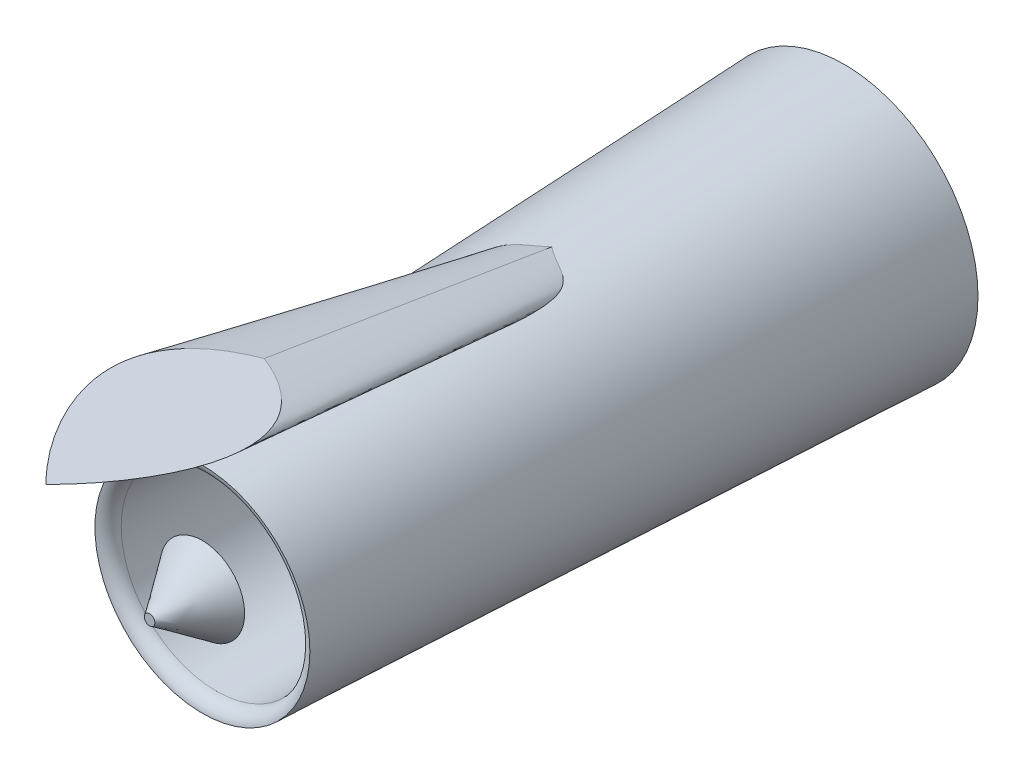
SolidWorks part; units mm, degrees
ref_plane "Front Plane" through (0, 0, 0) normal (0, 0, 1) x (1, 0, 0)
ref_plane "Top Plane" through (0, 0, 0) normal (0, 1, 0) x (1, 0, 0)
ref_plane "Right Plane" through (0, 0, 0) normal (1, 0, 0) x (0, 0, -1)
sketch "Sketch2" plane through (0, 0, 0) normal (0, 1, 0) x (1, 0, 0)
  line L0 (0, -5194.446) -> (0, 1731.482)
  line L1 (0, 0) -> (-18096.1342, 0) construction
  line L2 (0, 0) -> (-22098, -13277.818) construction
  line L3 (-22098, -15095.8741) -> (-22098, -12671.7993)
  line L4 (-22098, -12671.7993) -> (0, 1731.482)
  line L5 (-22098, -15095.8741) -> (0, -5194.446)
  line L6 (-9275.7037, -4314.3398) -> (-9275.7037, -5573.4051) construction
  line L7 (-9275.7037, -5573.4051) -> (-9275.7037, -9350.601) construction
  line L8 (-9275.7037, -5573.4051) -> (0, -5573.4051) construction
  line L9 (0, 346.2964) -> (-6827.52, -3825.6374)
  line L10 (0, -29565.6) -> (-7316.724, -34881.5112) construction
  line L11 (0, -29565.6) -> (-8167.6786, -29565.6) construction
  line L12 (0, -28507.0982) -> (0, -32741.1055)
  line L13 (-7316.724, -35992.9378) -> (-7316.724, -34511.0356)
  line L14 (-7316.724, -34511.0356) -> (0, -28507.0982)
  line L15 (0, -32741.1055) -> (-7316.724, -35992.9378)
  line L16 (-2399.2704, -30475.8849) -> (-2399.2704, -31308.772) construction
  line L17 (-2399.2704, -31308.772) -> (-2399.2704, -33807.4331) construction
  line L18 (-2399.2704, -31308.772) -> (0, -31308.772) construction
  line L19 (-6827.52, -3825.6374) -> (-6827.52, -6593.1427)
  line L20 (-6827.52, -6593.1427) -> (0, -3116.6676)
  line L21 (0, 346.2964) -> (0, -3116.6676) construction
  line L22 (0, -3116.6676) -> (0, 346.2964) construction
  line L23 (0, 346.2964) -> (0, -1385.1856) construction
  line L24 (0, 346.2964) -> (0, -3116.6676) construction
  line L25 (0, -1385.1856) -> (-6827.52, -5209.39) construction
  line L26 (0, 346.2964) -> (-22098, -13156.6142) construction
  line L27 (-3160.776, -1585.0854) -> (-3160.776, -3155.5874) construction
  line L28 (-3160.776, -3155.5874) -> (-3160.776, -4726.0893) construction
  line L29 (-3160.776, -3155.5874) -> (0, -3155.5874) construction
  dimension "Wing Sweep" = 31
  dimension "Half Span" = 22098
  dimension "Wing Root" = 6925.928
  dimension "D4" = 1731.482
  dimension "Wing Tip" = 2424.0748
  dimension "D6" = 606.0187
  dimension "Wing YBar" = 9275.7037
  dimension "Tail Sweep" = 36
  dimension "Tail Root" = 4234.0073
  dimension "D10" = 1058.5018
  dimension "Tail Tip" = 1481.9022
  dimension "D12" = 370.4756
  dimension "D13" = 7316.724
  dimension "Tail Ybar" = 2399.2704
  dimension "First Spar" = 1385.1856
  dimension "Second Spar" = 4848.1496
  dimension "Fuel Tip" = 2767.5053
  dimension "Tip Spar" = 484.815
  dimension "Fuel Ybar" = 3160.776
  dimension "Fuel Tank Length" = 6827.52
  dimension "Tail Arm" = 29565.6
sketch "Sketch4" plane through (0, 0, 0) normal (0, 1, 0) x (1, 0, 0)
  line L0 (0, 18200.9949) -> (0, -34834.2051) construction
  line L1 (-2240.28, 18200.9949) -> (2240.28, 18200.9949) construction
  line L2 (-2240.28, 11480.1549) -> (-2240.28, -25873.0851)
  line L3 (-2240.28, -34834.2051) -> (2240.28, -34834.2051) construction
  line L4 (2240.28, 11480.1549) -> (2240.28, -25873.0851)
  line L5 (0, -5194.446) -> (0, 1731.482) construction
  line L6 (-9275.7037, -5573.4051) -> (0, -5573.4051) construction
  line L7 (-2399.2704, -31308.772) -> (0, -31308.772) construction
  line L8 (0, 0) -> (-22098, -13277.818) construction
  line L9 (-22098, -12671.7993) -> (0, 1731.482) construction
  line L10 (-8451.85, 1616.4392) -> (-6132.83, 1616.4392)
  line L11 (-8451.85, 1616.4392) -> (-8451.85, -3941.0808)
  line L12 (-8451.85, -3941.0808) -> (-6132.83, -3941.0808)
  line L13 (-6132.83, 1616.4392) -> (-6132.83, -3941.0808)
  line L14 (2240.28, 11480.1549) -> (-2240.28, 11480.1549)
  arc A0 (-2240.28, -25873.0851) -> (2240.28, -25873.0851) centre (0, -25873.0851) ccw construction
  spline S0 degree 2 poles (-2240.28, 11480.1549) (-2010.8321, 15064.3252) (0, 18200.9949) knots 0 0 0 1 1 1 construction
  spline S1 degree 2 poles (2240.28, 11480.1549) (2010.8321, 15064.3252) (0, 18200.9949) knots 0 0 0 1 1 1 construction
  spline S2 degree 3 poles (-2240.28, -25873.0851) (-2042.135, -27711.7659) (-2075.1921, -30173.7144) (-919.8513, -32825.3563) (0, -32741.1055) knots 0 0 0 0 0.711043 1 1 1 1 construction
  spline S3 degree 3 poles (2240.28, -25873.0851) (2042.135, -27711.7659) (2075.1921, -30173.7144) (919.8513, -32825.3563) (0, -32741.1055) knots 0 0 0 0 0.711043 1 1 1 1 construction
  spline S4 degree 2 poles (-2240.28, -25873.0851) (-2027.1744, -27637.7456) (0, -27753.3552) knots 0 0 0 1 1 1
  spline S5 degree 2 poles (2240.28, -25873.0851) (2027.1744, -27637.7456) (0, -27753.3552) knots 0 0 0 1 1 1
  point P6 (0, 11480.1549)
  point P7 (0, -25873.0851)
  point P8 (0, -5573.4051)
  point P15 (0, -28113.3651)
  point P28 (-7292.34, 1616.4392)
  point P29 (-7292.34, -3021.6008)
  point P35 (-7292.34, -4381.6799)
  point P44 (-7292.34, -606.5688)
  dimension "Fuse Length" = 53035.2
  dimension "Fuse Dia" = 4480.56
  dimension "D3" = 6720.84
  dimension "D4" = 8961.12
  dimension "D6" = 7292.34
  dimension "Engine Dia" = 2319.02
  dimension "Engine Length" = 5557.52
  dimension "D9" = 4638.04
  dimension "D10" = 2223.008
  dimension "D11" = 4966.8362
  dimension "D2" = 23774.4
ref_plane "Plane1" through (0, 609.6, 0) normal (0, 1, 0) x (1, 0, 0)
sketch "Sketch10" plane through (0, 0, 0) normal (0, 1, 0) x (1, 0, 0)
  line L0 (-22098, -12671.7993) -> (-2240.28, 271.2873)
  line L1 (-2240.28, 11480.1549) -> (-2240.28, -25873.0851) construction
  line L2 (-22098, -12671.7993) -> (-22098, -15095.8741)
  line L3 (-22098, -15095.8741) -> (-7292.34, -8461.9172)
  line L4 (-7292.34, -8461.9172) -> (-2240.28, -8461.9172)
  line L5 (-22098, -15095.8741) -> (0, -5194.446) construction
  line L6 (-22098, -12671.7993) -> (0, 1731.482) construction
  line L7 (-2240.28, -8461.9172) -> (-2240.28, 271.2873) construction
  line L9 (0, 271.2873) -> (0, -8461.9172)
  line L10 (0, -8461.9172) -> (-2240.28, -8461.9172)
  line L11 (0, -5194.446) -> (0, 1731.482) construction
  line L12 (-2240.28, 271.2873) -> (0, 1731.482)
  line L13 (0, 1731.482) -> (0, 271.2873)
ref_plane "Plane4" through (13979.3336, 0, 17035.9747) normal (0.6343, 0, 0.773) x (0.773, 0, -0.6343)
ref_plane "Plane2" through (-7316.724, 0, 0) normal (1, 0, 0) x (0, 0, -1)
ref_plane "Plane5" through (0, 0, -1616.4392) normal (0, 0, 1) x (1, 0, 0)
ref_plane "Plane6" through (0, 0, 3941.0808) normal (0, 0, 1) x (1, 0, 0)
ref_plane "Plane7" through (-7292.34, 0, 0) normal (1, 0, 0) x (0, 0, -1)
sketch "Sketch13" plane through (0, 0, -1616.4392) normal (0, 0, 1) x (1, 0, 0)
  line L1 (-8451.85, 0) -> (-6132.83, 0) construction
  line L2 (-7292.34, 0) -> (-6132.83, 0) construction
  line L3 (-7292.34, 0) -> (-7292.34, -1159.51) construction
  circle A0 centre (-7292.34, 0) radius 1159.51
sketch "Sketch14" plane through (0, 0, 3941.0808) normal (0, 0, 1) x (1, 0, 0)
  line L0 (-8451.85, 0) -> (-6132.83, 0) construction
  line L1 (-7292.34, 0) -> (-6361.43, 0) construction
  line L2 (-7292.34, 0) -> (-7292.34, -930.91) construction
  line L3 (-7292.34, 0) -> (-7249.9946, 929.9464) construction
  circle A0 centre (-7292.34, 0) radius 930.91
  point P2 (-7190.2668, 925.297)
  dimension "D1" = 228.6
sketch "Sketch15" plane through (-7292.34, 0, 0) normal (1, 0, 0) x (0, 0, -1)
  line L0 (1616.4392, 0) -> (-3941.0808, 0) construction
  line L1 (1616.4392, 0) -> (-3941.0808, 0) construction
  line L2 (1616.4392, 0) -> (1616.4392, -1159.51) construction
  line L3 (-3941.0808, 0) -> (-3941.0808, -930.91) construction
  line L6 (1616.4392, -1159.51) -> (-3941.0808, -930.91) construction
  line L7 (1616.4392, -1159.51) -> (-5492.1559, -1159.51) construction
  spline S0 degree 2 poles (1616.4392, -1159.51) (-1167.6686, -1217.6329) (-3941.0808, -930.91) knots 0 0 0 1 1 1
loft "Loft2" add profiles "Sketch13", "Sketch14" connector at (-6132.83, 0, -1616.4392) connector at (-6361.43, 0, 3941.0808)
sketch "Sketch16" plane through (0, 0, -1616.4392) normal (0, 0, -1) x (-1, 0, 0)
  circle A0 centre (7292.34, 0) radius 824.23
  circle A1 centre (7292.34, 0) radius 1159.51 construction
  circle A2 centre (7292.34, 0) radius 930.91 construction
  dimension "D1" = 106.68
extrude "Cut-Extrude1" cut sketch "Sketch16" against normal through all both and the other way through all
fillet "Fillet1" radius 304.8 1 edges at (-6468.11, 0, -1616.4392)
fillet "Fillet2" radius 121.92 1 edges at (-6468.11, 0, 3941.0808)
ref_plane "Plane8" through (0, 929.9464, 0) normal (0, 1, 0) x (1, 0, 0)
sketch "Sketch17" plane through (0, 929.9464, 0) normal (0, 1, 0) x (1, 0, 0)
  line L0 (-7292.34, 1616.4392) -> (-7292.34, -3941.0808) construction
  line L1 (-8451.85, 1616.4392) -> (-6132.83, 1616.4392) construction
  line L2 (-8451.85, -3941.0808) -> (-6132.83, -3941.0808) construction
  spline S0 degree 3 poles (-7292.34, -149.3688) (-6646.0952, -977.1535) (-7181.4944, -1981.2715) (-7292.34, -2877.7155) knots 0 0 0 0 1 1 1 1
  spline S1 degree 3 poles (-7292.34, -149.3688) (-7938.5848, -977.1535) (-7403.1856, -1981.2715) (-7292.34, -2877.7155) knots 0 0 0 0 1 1 1 1
  point P8 (0, 0)
  point P10 (-7622.5941, -572.496)
  point P12 (-6895.0676, -1095.3473)
  point P13 (-7797.547, -763.3649)
  point P14 (-7592.9344, -1966.3159)
  point P15 (-7292.34, -2877.7155)
  point P19 (-7292.34, 155.4312)
  point P20 (-7597.0591, -921.2681)
  point P21 (-7440.954, -2143.7105)
  dimension "D1" = 457.2
sketch "Sketch18" plane through (0, 0, 3941.0808) normal (0, 0, 1) x (1, 0, 0)
  circle A0 centre (-7292.34, 0) radius 365.76
  dimension "D1" = 731.52
ref_plane "Plane9" through (0, 0, 4398.2808) normal (0, 0, 1) x (1, 0, 0)
sketch "Sketch19" plane through (0, 0, 4398.2808) normal (0, 0, 1) x (1, 0, 0)
  circle A0 centre (-7292.34, 0) radius 45.72
  dimension "D1" = 91.44
loft "Loft3" add profiles "Sketch19", "Sketch18" connector at (-7325.9035, 31.0453, 4398.2808) connector at (-7425.7022, 340.5802, 3941.0808)
ref_plane "Plane10" through (0, 1463.3464, 0) normal (0, 1, 0) x (1, 0, 0)
sketch "Sketch20" plane through (0, 1463.3464, 0) normal (0, 1, 0) x (1, 0, 0)
  line L0 (-7292.34, -3406.1504) -> (-7292.34, -5295.5283) construction
  line L1 (-7292.34, 1616.4392) -> (-7292.34, -3941.0808) construction
  spline S0 degree 3 poles (-7292.34, -3406.1504) (-6242.025, -3812.9933) (-6806.4277, -4813.3352) (-7292.34, -5295.5283) knots 0 0 0 0 1 1 1 1
  spline S1 degree 3 poles (-7292.34, -3406.1504) (-8342.655, -3812.9933) (-7778.2523, -4813.3352) (-7292.34, -5295.5283) knots 0 0 0 0 1 1 1 1
  point P2 (-6825.4307, -3639.1239)
  point P4 (-7292.34, -4889.6609)
  point P10 (-7292.34, -3406.1504)
  point P11 (-6907.1599, -4032.5433)
  point P12 (-7292.34, -5295.5283)
  point P13 (-6942.7987, -4859.1372)
  point P14 (-6698.2367, -4163.3361)
loft "Loft4" add profiles "Sketch20", "Sketch17" connector at (-7292.34, 1463.3464, 3406.1504) connector at (-7292.34, 929.9464, 149.3688)
ref_plane "Plane11" through (0, 1097.5864, 0) normal (0, 1, 0) x (1, 0, 0)
sketch "Sketch21" plane through (0, 1097.5864, 0) normal (0, 1, 0) x (1, 0, 0)
  line L0 (-6132.83, 1616.4392) -> (-6132.83, -3941.0808) construction
  line L1 (-6132.83, 1616.4392) -> (-8451.85, 1616.4392)
  line L2 (-6132.83, 1616.4392) -> (-6132.83, -3941.0808)
  line L3 (-6132.83, -3941.0808) -> (-8451.85, -3941.0808)
  line L4 (-8451.85, 1616.4392) -> (-8451.85, -3941.0808)
  line L5 (-8451.85, 1616.4392) -> (-8451.85, -3941.0808) construction
  line L6 (-8451.85, -3941.0808) -> (-6132.83, -3941.0808) construction
  point P4 (0, 0)
  point P5 (0, 0)
  point P8 (0, 0)
  point P9 (-5711.4236, 2620.3231)
  point P11 (-6493.51, 4159.5558)
  dimension "D2" = 0
equation "\"D6@Sketch2\" = \"Wing Tip@Sketch2\" / 4"
equation "\"D4@Sketch2\" = \"Wing Root@Sketch2\" / 4"
equation "\"D10@Sketch2\" = \"Tail Root@Sketch2\" / 4"
equation "\"D12@Sketch2\" = \"Tail Tip@Sketch2\" / 4"
equation "\"D13@Sketch2\"=48.01/2"
equation "\"First Spar@Sketch2\"=0.2 * \"Wing Root@Sketch2\""
equation "\"Second Spar@Sketch2\"   = 0.7 * \"Wing Root@Sketch2\""
equation "\"Tip Spar@Sketch2\"=0.2 * \"Wing Tip@Sketch2\""
equation "\"D3@Sketch4\" = 1.5 * \"Fuse Dia@Sketch4\""
equation "\"D4@Sketch4\" = 2 * \"Fuse Dia@Sketch4\""
equation "\"D6@Sketch4\" = 0.33 * \"Half Span@Sketch2\""
equation "\"D9@Sketch4\" = 2 * \"Engine Dia@Sketch4\""
equation "\"D10@Sketch4\" = 0.40 * \"Engine Length@Sketch4\""
